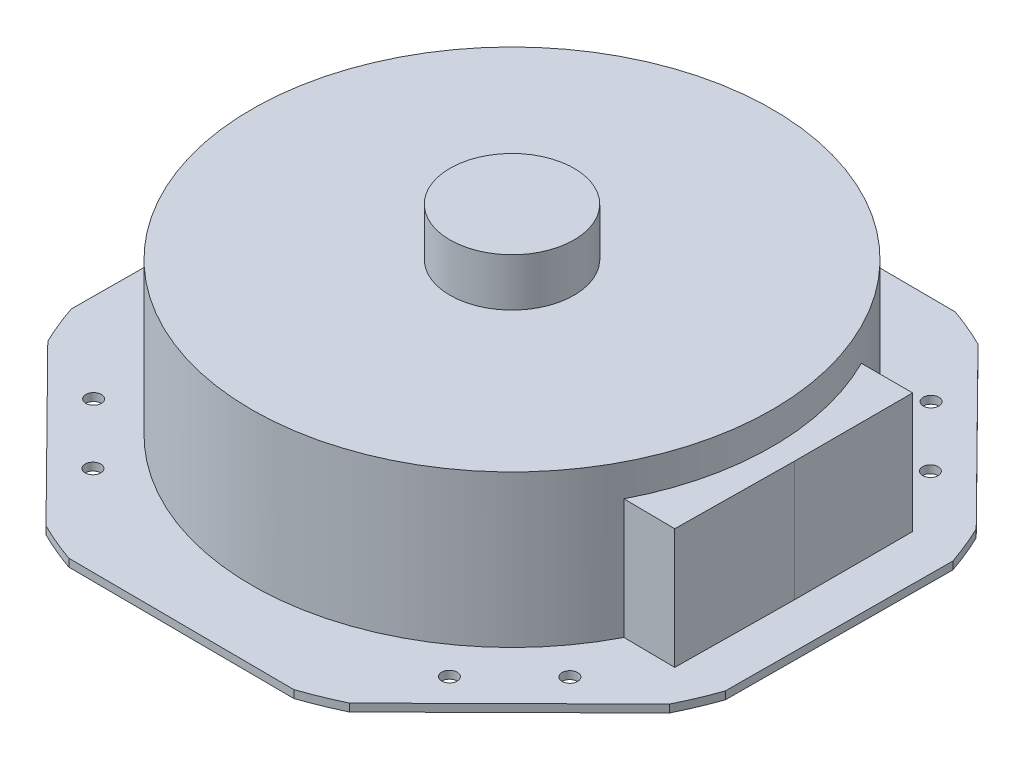
SolidWorks part; units mm, degrees
ref_plane "前视基准面" through (0, 0, 0) normal (0, 0, 1) x (1, 0, 0)
ref_plane "上视基准面" through (0, 0, 0) normal (0, 1, 0) x (1, 0, 0)
ref_plane "右视基准面" through (0, 0, 0) normal (1, 0, 0) x (0, 0, -1)
sketch "草图2" plane through (0, 0, 0) normal (0, 1, 0) x (1, 0, 0)
  line L1 (177.9711, 422.9703) -> (-173.2406, 424.9297)
  line L2 (-173.2406, 424.9297) -> (-422.9703, 177.9711)
  line L3 (-422.9703, 177.9711) -> (-424.9297, -173.2406)
  line L4 (-424.9297, -173.2406) -> (-177.9711, -422.9703)
  line L5 (-177.9711, -422.9703) -> (173.2406, -424.9297)
  line L6 (173.2406, -424.9297) -> (422.9703, -177.9711)
  line L7 (422.9703, -177.9711) -> (424.9297, 173.2406)
  line L8 (424.9297, 173.2406) -> (177.9711, 422.9703)
  circle A0 centre (0, 0) radius 423.9566 construction
  circle A1 centre (0, 0) radius 448.35
  dimension "D2" = 896.7
  dimension "D1" = 847.9
extrude "凸台-拉伸1" add sketch "草图2" along normal blind 10 contours L5 A1 L6 L7 L8 L1 L2 L3 L4 region at (0, 0, 0)
sketch "草图3" plane through (0, 10, 0) normal (0, 1, 0) x (1, 0, 0)
  circle A0 centre (0, 0) radius 335.5
  dimension "D1" = 671
extrude "凸台-拉伸4" add sketch "草图3" along normal blind 196 separate body
sketch "草图6" plane through (0, 10, 0) normal (0, 1, 0) x (1, 0, 0)
  line L0 (0, 0) -> (423.95, -2.3653) construction
  line L1 (423.1362, -148.2346) -> (424.7638, 143.5041) construction
  line L2 (366, -2.042) -> (366, 150.4604)
  line L3 (366, 150.4604) -> (299.8698, 150.4604)
  line L4 (364.2984, -154.5348) -> (298.1723, -153.797)
  line L5 (366, -2.042) -> (364.2984, -154.5348)
  circle A0 centre (0, 0) radius 335.5 construction
  circle A1 centre (0, 0) radius 335.5
  point P10 (298.1723, 153.797)
  dimension "D1" = 305
  dimension "D2" = 366
extrude "凸台-拉伸5" add sketch "草图6" along normal blind 154.8 separate body contours L0 A1 L4 L5 | A1 L0 L2 L3 region at (343.6948, 10, -84.9068) region at (342.726, 10, 88.7364)
combine bodies "组合1" operation type add bodies to combine 104 105
shell "抽壳3" thickness 5 removed face at (211.9649, 10, 1.1826)
sketch "草图7" plane through (0, 10, 0) normal (0, -1, 0) x (1, 0, 0)
  line L0 (361, 2.0141) -> (359.3545, 149.4794) construction
  line L1 (361, 2.0141) -> (359.3545, 149.4794) construction
  line L2 (359.3545, 149.4794) -> (295.127, 148.7627) construction
  line L3 (359.3545, 149.4794) -> (295.127, 148.7627) construction
  line L4 (361, 2.0141) -> (361, -145.4604) construction
  line L5 (361, 2.0141) -> (361, -145.4604) construction
  line L6 (361, -145.4604) -> (296.7685, -145.4604) construction
  line L7 (361, -145.4604) -> (296.7685, -145.4604) construction
  line L8 (354.4106, 144.4239) -> (292.0488, 143.728)
  line L9 (356, -140.4604) -> (293.6343, -140.4604)
  line L10 (356, 1.9862) -> (356, -140.4604)
  line L11 (356, 1.9862) -> (354.4106, 144.4239)
  arc A0 (295.127, 148.7627) -> (296.7685, -145.4604) centre (0, 0) ccw construction
  arc A1 (295.127, 148.7627) -> (296.7685, -145.4604) centre (0, 0) ccw construction
  arc A2 (292.0488, 143.728) -> (293.6343, -140.4604) centre (0, 0) ccw
  dimension "D1" = 5
extrude "切除-拉伸1" cut sketch "草图7" along normal blind 154.8
combine bodies "组合2" operation type add bodies to combine 106 107
sketch "草图8" plane through (0, 206, 0) normal (0, 1, 0) x (1, 0, 0)
  circle A0 centre (0, 0) radius 80
  dimension "D1" = 160
extrude "凸台-拉伸7" add sketch "草图8" along normal offset from surface (61.8 mm away) 267.8 up to face at (0, 0, 0)
sketch "草图9" plane through (0, 201, 0) normal (0, -1, 0) x (-1, 0, 0)
  circle A0 centre (0, 0) radius 80
  dimension "D1" = 160
extrude "凸台-拉伸8" add sketch "草图9" along normal offset from surface (123.6 mm away) 77.4 contours A0 up to face at (0, 0, 0)
sketch "草图10" plane through (0, 77.4, 0) normal (0, -1, 0) x (1, 0, 0)
  circle A2 centre (0, 0) radius 75
  circle A3 centre (0, 0) radius 75
  dimension "D1" = 5
extrude "切除-拉伸2" cut sketch "草图10" against normal offset from surface (185.4 mm away) 5 up to face at (0, 267.8, 80)
sketch "草图11" plane through (0, 206, 0) normal (0, 1, 0) x (1, 0, 0)
  line L0 (-229.3401, 309.9906) -> (-307.4123, 232.7846) construction
  line L1 (-268.3762, 271.3876) -> (-298.1054, 301.4504) construction
  line L2 (-194.3848, 404.0202) -> (-401.8261, 198.8807) construction
  circle A0 centre (-229.3401, 309.9906) radius 10
  circle A1 centre (-307.4123, 232.7846) radius 10
  dimension "D1" = 20
  dimension "D2" = 20
  dimension "D3" = 42.28
  dimension "D4" = 109.8
extrude "切除-拉伸4" cut sketch "草图11" against normal blind 1000
pattern_circular "阵列(圆周)1" count 4 over 360 about axis through (0, 206, 0) along (0, -1, 0) of "切除-拉伸4" reverse direction yes
